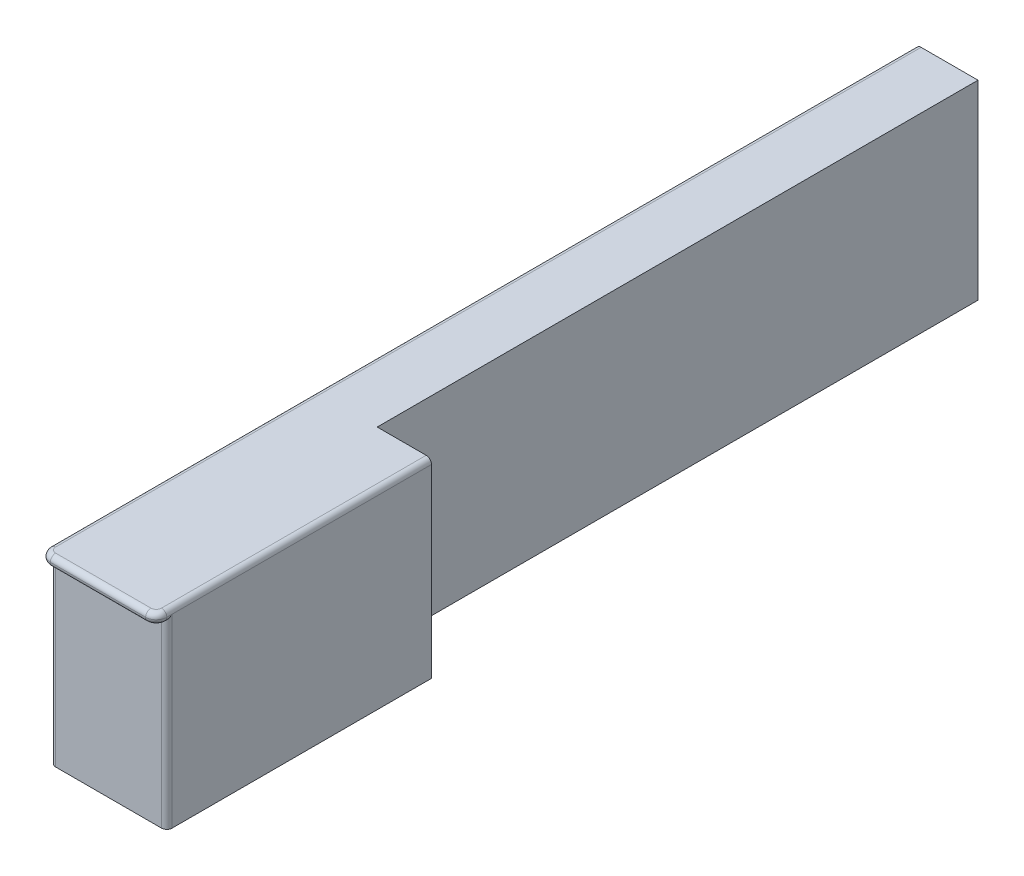
SolidWorks part; units mm, degrees
ref_plane "Front Plane" through (0, 0, 0) normal (0, 0, 1) x (1, 0, 0)
ref_plane "Top Plane" through (0, 0, 0) normal (0, 1, 0) x (1, 0, 0)
ref_plane "Right Plane" through (0, 0, 0) normal (1, 0, 0) x (0, 0, -1)
sketch "Sketch1" plane through (0, 0, 0) normal (0, 1, 0) x (1, 0, 0)
  line L1 (-11, -81.75) -> (11, -81.75)
  line L2 (-11, -81.75) -> (-11, 81.75)
  line L3 (-11, 81.75) -> (11, 81.75)
  line L4 (11, -81.75) -> (11, 81.75)
  line L5 (-11, -81.75) -> (11, 81.75) construction
  line L6 (-11, 81.75) -> (11, -81.75) construction
  point P0 (0, 0)
  dimension "D1" = 163.5
  dimension "D2" = 22
extrude "Boss-Extrude1" add sketch "Sketch1" along normal blind 36 contours L2 L3 L4 L1
fillet "Fillet1" radius 1 2 edges at (-11, 18, 81.75) (11, 18, 81.75)
sketch "Sketch2" plane through (0, 36, 0) normal (0, 1, 0) x (1, 0, 0)
  line L0 (11, -80.75) -> (11, 81.75) construction
  line L1 (-11, 81.75) -> (11, 81.75)
  line L2 (-11, 81.75) -> (-11, -83.75)
  line L3 (-11, -83.75) -> (11, -83.75)
  line L4 (11, 81.75) -> (11, -83.75)
  line L5 (-10, -81.75) -> (10, -81.75) construction
  dimension "D1" = 2
extrude "Boss-Extrude2" add sketch "Sketch2" against normal blind 2
fillet "Fillet2" radius 2 2 edges at (-11, 35, 83.75) (11, 35, 83.75)
fillet "Fillet3" radius 1 10 edges at (-11, 34, 81.25) (-10.4142, 34, 83.1642) (11, 34, 81.25) (10.4142, 34, 83.1642) (11, 36, 0) (10.4142, 36, 83.1642) (0, 36, 83.75) (-10.4142, 36, 83.1642) (-11, 36, 0) (0, 34, 83.75)
sketch "Sketch3" plane through (0, 36, 0) normal (0, 1, 0) x (1, 0, 0)
  line L1 (7.5, -31.75) -> (11, -31.75)
  line L2 (7.5, -31.75) -> (7.5, 81.75)
  line L3 (7.5, 81.75) -> (11, 81.75)
  line L4 (11, -31.75) -> (11, 81.75)
  line L5 (7.5, -31.75) -> (11, 81.75) construction
  line L6 (7.5, 81.75) -> (11, -31.75) construction
  line L7 (-10, -81.75) -> (10, -81.75) construction
  line L8 (-11, 81.75) -> (11, 81.75) construction
  line L9 (11, 81.75) -> (11, -80.75) construction
  dimension "D1" = 3.5
  dimension "D2" = 50
extrude "Cut-Extrude2" [suppressed] cut sketch "Sketch3" against normal through all
sketch "Sketch5" plane through (-11, 0, 0) normal (-1, 0, 0) x (0, 0, 1)
  line L0 (81.75, 34) -> (81.75, 0) construction
  line L1 (80.75, 0) -> (-81.75, 0) construction
  line L2 (-81.75, 36) -> (81.75, 36) construction
  line L3 (-81.75, 35) -> (-81.75, 0) construction
  line L8 (31.75, 36) -> (-81.75, 36)
  line L9 (31.75, 0) -> (31.75, 36)
  line L10 (-81.75, 0) -> (31.75, 0)
  line L11 (-81.75, 36) -> (-81.75, 0)
  dimension "D1" = 50
extrude "Cut-Extrude4" [suppressed] cut sketch "Sketch5" against normal blind 3.5
sketch "Sketch4" [suppressed] plane through (7.5, 0, 0) normal (1, 0, 0) x (0, 0, -1)
  line L4 (81.75, 36) -> (-31.75, 36)
  line L5 (-31.75, 36) -> (-31.75, 0)
  line L6 (-31.75, 0) -> (81.75, 0)
  line L7 (81.75, 0) -> (81.75, 36)
  line L8 (81.75, 36) -> (-31.75, 36)
  line L9 (-31.75, 36) -> (-31.75, 0)
  line L10 (-31.75, 0) -> (81.75, 0)
  line L11 (81.75, 0) -> (81.75, 36)
  dimension "D1" = 0
extrude "Cut-Extrude3" [suppressed] cut sketch "Sketch4" against normal blind 3.25
sketch "Sketch6" [suppressed] plane through (-7.5, 0, 0) normal (-1, 0, 0) x (0, 0, 1)
  line L4 (-81.75, 36) -> (-81.75, 0)
  line L5 (-81.75, 0) -> (31.75, 0)
  line L6 (31.75, 0) -> (31.75, 36)
  line L7 (31.75, 36) -> (-81.75, 36)
  line L8 (-81.75, 36) -> (-81.75, 0)
  line L9 (-81.75, 0) -> (31.75, 0)
  line L10 (31.75, 0) -> (31.75, 36)
  line L11 (31.75, 36) -> (-81.75, 36)
  dimension "D1" = 0
extrude "Cut-Extrude5" [suppressed] cut sketch "Sketch6" against normal blind 3.25
sketch "White" plane through (0, 0, 0) normal (0, 1, 0) x (1, 0, 0)
  line L0 (12.5, -81.75) -> (34.5, -81.75)
  line L1 (-11, -81.75) -> (11, -81.75)
  line L2 (-11, -81.75) -> (-11, 81.75)
  line L3 (-11, 81.75) -> (11, 81.75)
  line L4 (11, -81.75) -> (11, 81.75)
  line L5 (12.5, -81.75) -> (12.5, 81.75)
  line L6 (12.5, 81.75) -> (34.5, 81.75)
  line L7 (34.5, -81.75) -> (34.5, 81.75)
  line L8 (36, -81.75) -> (58, -81.75)
  line L9 (36, -81.75) -> (36, 81.75)
  line L10 (36, 81.75) -> (58, 81.75)
  line L11 (58, -81.75) -> (58, 81.75)
  line L12 (59.5, -81.75) -> (81.5, -81.75)
  line L13 (59.5, -81.75) -> (59.5, 81.75)
  line L14 (59.5, 81.75) -> (81.5, 81.75)
  line L15 (81.5, -81.75) -> (81.5, 81.75)
  line L16 (83, -81.75) -> (105, -81.75)
  line L17 (83, -81.75) -> (83, 81.75)
  line L18 (83, 81.75) -> (105, 81.75)
  line L19 (105, -81.75) -> (105, 81.75)
  line L20 (106.5, -81.75) -> (128.5, -81.75)
  line L21 (106.5, -81.75) -> (106.5, 81.75)
  line L22 (106.5, 81.75) -> (128.5, 81.75)
  line L23 (128.5, -81.75) -> (128.5, 81.75)
  line L24 (130, -81.75) -> (152, -81.75)
  line L25 (130, -81.75) -> (130, 81.75)
  line L26 (130, 81.75) -> (152, 81.75)
  line L27 (152, -81.75) -> (152, 81.75)
  dimension "D1" = 7
sketch "Black" plane through (0, 0, 0) normal (0, 1, 0) x (1, 0, 0)
  line L0 (-11, 81.75) -> (11, 81.75) construction
  line L1 (16, -31.75) -> (4, -31.75)
  line L2 (16, -31.75) -> (16, 81.75)
  line L3 (16, 81.75) -> (4, 81.75)
  line L4 (4, -31.75) -> (4, 81.75)
  line L6 (31, -31.75) -> (43, -31.75)
  line L7 (31, -31.75) -> (31, 81.75)
  line L8 (31, 81.75) -> (43, 81.75)
  line L9 (43, -31.75) -> (43, 81.75)
  line L10 (12.5, -81.75) -> (34.5, -81.75) construction
  line L11 (16, -31.75) -> (31, -31.75) construction
  line L12 (36, 81.75) -> (58, 81.75) construction
  line L13 (106.5, 81.75) -> (128.5, 81.75) construction
  line L14 (111.75, 81.75) -> (99.75, 81.75)
  line L15 (111.75, 81.75) -> (111.75, -31.75)
  line L16 (111.75, -31.75) -> (99.75, -31.75)
  line L17 (99.75, 81.75) -> (99.75, -31.75)
  line L18 (83, 81.75) -> (105, 81.75) construction
  line L19 (126.75, 81.75) -> (138.75, 81.75)
  line L20 (126.75, 81.75) -> (126.75, -31.75)
  line L21 (126.75, -31.75) -> (138.75, -31.75)
  line L22 (138.75, 81.75) -> (138.75, -31.75)
  line L23 (84.75, 81.75) -> (72.75, 81.75)
  line L24 (84.75, 81.75) -> (84.75, -31.75)
  line L25 (84.75, -31.75) -> (72.75, -31.75)
  line L26 (72.75, 81.75) -> (72.75, -31.75)
  line L27 (105, -81.75) -> (106.5, -81.75) construction
  point P14 (23.5, -81.75)
  point P15 (23.5, -31.75)
  point P36 (105.75, -81.75)
  point P37 (105.75, -31.75)
  dimension "D1" = 50
  dimension "D2" = 12
  dimension "D3" = 12
  dimension "D4" = 15
  dimension "D5" = 15
  dimension "D6" = 15
sketch "Sketch11" plane through (0, 36, 0) normal (0, 1, 0) x (1, 0, 0)
  line L1 (11, 81.75) -> (2.5, 81.75)
  line L2 (11, 81.75) -> (11, -31.75)
  line L3 (11, -31.75) -> (2.5, -31.75)
  line L4 (2.5, 81.75) -> (2.5, -31.75)
  line L5 (16, -31.75) -> (4, -31.75) construction
  dimension "D1" = 8.5
extrude "C" [suppressed] cut sketch "Sketch11" against normal through all
sketch "Sketch12" plane through (0, 36, 0) normal (0, 1, 0) x (1, 0, 0)
  line L0 (31, -31.75) -> (43, -31.75) construction
  line L1 (-11, 81.75) -> (-6, 81.75)
  line L2 (-11, 81.75) -> (-11, -31.75)
  line L3 (-11, -31.75) -> (-6, -31.75)
  line L4 (-6, 81.75) -> (-6, -31.75)
  line L5 (11, 81.75) -> (6, 81.75)
  line L6 (11, 81.75) -> (11, -31.75)
  line L7 (11, -31.75) -> (6, -31.75)
  line L8 (6, 81.75) -> (6, -31.75)
  dimension "D1" = 5
  dimension "D2" = 5
extrude "D" [suppressed] cut sketch "Sketch12" against normal through all
sketch "Sketch13" plane through (0, 36, 0) normal (0, 1, 0) x (1, 0, 0)
  line L1 (-11, 81.75) -> (-2.5, 81.75)
  line L2 (-11, 81.75) -> (-11, -31.75)
  line L3 (-11, -31.75) -> (-2.5, -31.75)
  line L4 (-2.5, 81.75) -> (-2.5, -31.75)
  line L5 (16, -31.75) -> (4, -31.75) construction
  dimension "D1" = 8.5
extrude "E" [suppressed] cut sketch "Sketch13" against normal through all
sketch "Sketch14" plane through (0, 36, 0) normal (0, 1, 0) x (1, 0, 0)
  line L0 (16, -31.75) -> (4, -31.75) construction
  line L1 (11, 81.75) -> (0.75, 81.75)
  line L2 (11, 81.75) -> (11, -31.75)
  line L3 (11, -31.75) -> (0.75, -31.75)
  line L4 (0.75, 81.75) -> (0.75, -31.75)
  dimension "D1" = 10.25
extrude "F" cut sketch "Sketch14" against normal through all
sketch "Sketch15" plane through (0, 36, 0) normal (0, 1, 0) x (1, 0, 0)
  line L1 (-11, 81.75) -> (-7.75, 81.75)
  line L2 (-11, 81.75) -> (-11, -31.75)
  line L3 (-11, -31.75) -> (-7.75, -31.75)
  line L4 (-7.75, 81.75) -> (-7.75, -31.75)
  line L5 (11, 81.75) -> (4.25, 81.75)
  line L6 (11, 81.75) -> (11, -31.75)
  line L7 (11, -31.75) -> (4.25, -31.75)
  line L8 (4.25, 81.75) -> (4.25, -31.75)
  line L9 (16, -31.75) -> (4, -31.75) construction
  dimension "D1" = 3.25
  dimension "D2" = 6.75
extrude "G" [suppressed] cut sketch "Sketch15" against normal through all
sketch "Sketch16" plane through (0, 36, 0) normal (0, 1, 0) x (1, 0, 0)
  line L0 (16, -31.75) -> (4, -31.75) construction
  line L1 (-11, 81.75) -> (-4.25, 81.75)
  line L2 (-11, 81.75) -> (-11, -31.75)
  line L3 (-11, -31.75) -> (-4.25, -31.75)
  line L4 (-4.25, 81.75) -> (-4.25, -31.75)
  line L5 (11, 81.75) -> (7.75, 81.75)
  line L6 (11, 81.75) -> (11, -31.75)
  line L7 (11, -31.75) -> (7.75, -31.75)
  line L8 (7.75, 81.75) -> (7.75, -31.75)
  dimension "D1" = 6.75
  dimension "D2" = 3.25
extrude "A" [suppressed] cut sketch "Sketch16" against normal through all
sketch "Sketch17" plane through (0, 36, 0) normal (0, 1, 0) x (1, 0, 0)
  line L0 (16, -31.75) -> (4, -31.75) construction
  line L1 (-11, 81.75) -> (-0.75, 81.75)
  line L2 (-11, 81.75) -> (-11, -31.75)
  line L3 (-11, -31.75) -> (-0.75, -31.75)
  line L4 (-0.75, 81.75) -> (-0.75, -31.75)
  dimension "D1" = 10.25
extrude "B" [suppressed] cut sketch "Sketch17" against normal through all
